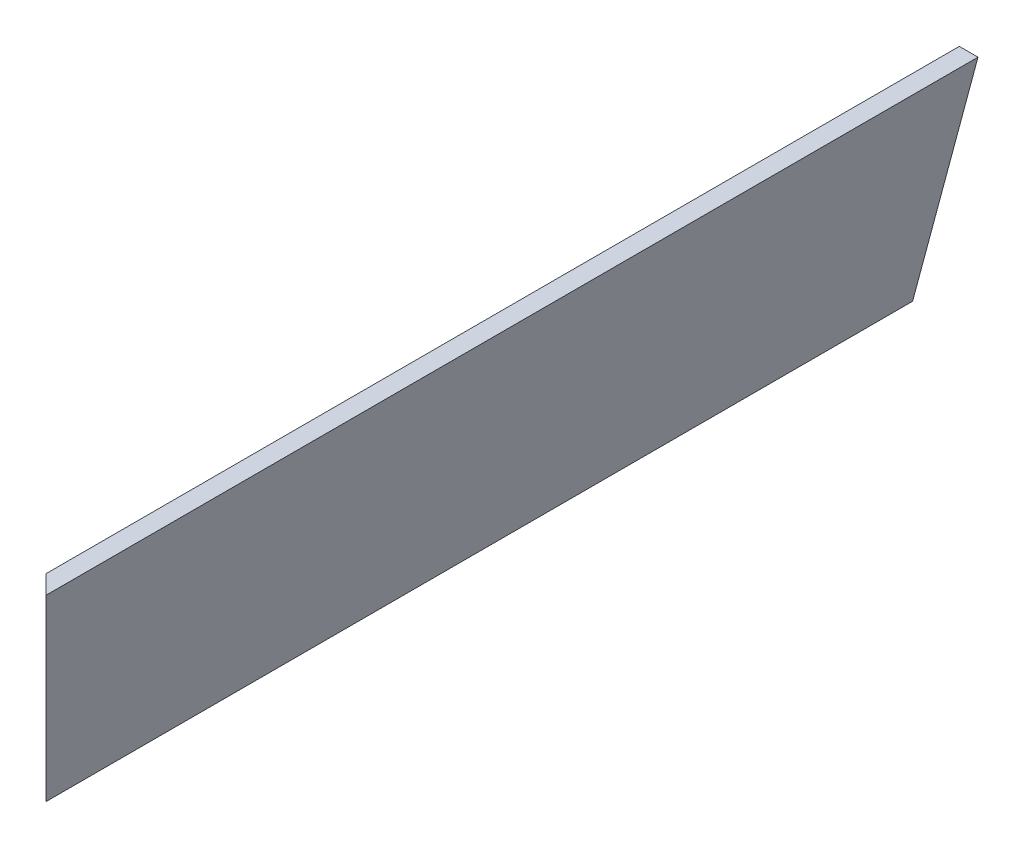
SolidWorks part; units mm, degrees
material "Cedar"
ref_plane "Front Plane" through (0, 0, 0) normal (0, 0, 1) x (1, 0, 0)
ref_plane "Top Plane" through (0, 0, 0) normal (0, 1, 0) x (1, 0, 0)
ref_plane "Right Plane" through (0, 0, 0) normal (1, 0, 0) x (0, 0, -1)
ref_plane "Plane1" through (0, 0, 0) normal (-0.7071, 0, 0.7071) x (0.7071, 0, 0.7071)
sketch "Sketch2" plane through (0, 0, 0) normal (0, 0, 1) x (1, 0, 0)
  line L0 (596.452, 0) -> (609.6, 0)
  line L1 (609.6, 0) -> (655.618, 171.7416)
  line L2 (655.618, 171.7416) -> (642.47, 171.7416)
  line L3 (642.47, 171.7416) -> (596.452, 0)
  line L4 (0, 0) -> (596.452, 0) construction
  line L5 (596.452, 0) -> (596.452, 177.6975) construction
  dimension "D1" = 15
  dimension "D2" = 12.7
  dimension "D3" = 177.8
  dimension "D4" = 609.6
extrude "Boss-Extrude1" add sketch "Sketch2" along normal up to surface (655.618 mm away) up to plane "Plane1"
mirror "Mirror1" [suppressed] about plane through (0, 0, 0) normal (-0.7071, 0, 0.7071)
ref_plane "Plane2" [suppressed] through (609.6, 0, 609.6) normal (0.2506, 0.9351, 0.2506) x (0.9681, -0.242, -0.0649)
